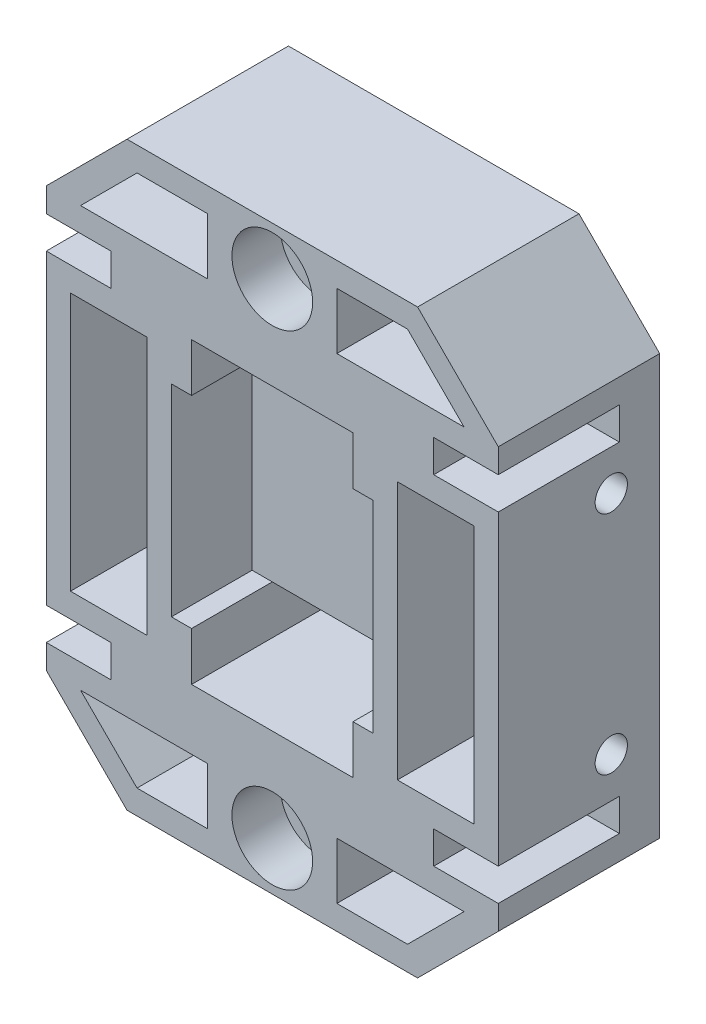
SolidWorks part; units mm, degrees
ref_plane "Plano frontal" through (0, 0, 0) normal (0, 0, 1) x (1, 0, 0)
ref_plane "Plano superior" through (0, 0, 0) normal (0, 1, 0) x (1, 0, 0)
ref_plane "Plano direito" through (0, 0, 0) normal (1, 0, 0) x (0, 0, -1)
sketch "Esboço1" plane through (0, 0, 0) normal (0, 0, 1) x (1, 0, 0)
  line L1 (-14, -18) -> (14, -18)
  line L2 (-14, -18) -> (-14, 18)
  line L3 (-14, 18) -> (14, 18)
  line L4 (14, -18) -> (14, 18)
  line L5 (-14, -18) -> (14, 18) construction
  line L6 (-14, 18) -> (14, -18) construction
  point P0 (0, 0)
  dimension "D1" = 28
  dimension "D2" = 36
extrude "Ressalto-extrusão1" add sketch "Esboço1" along normal blind 10
sketch "Esboço2" plane through (0, 0, 10) normal (0, 0, 1) x (1, 0, 0)
  line L1 (-6.25, -6.25) -> (6.25, -6.25)
  line L2 (-6.25, -6.25) -> (-6.25, 6.25)
  line L3 (-6.25, 6.25) -> (6.25, 6.25)
  line L4 (6.25, -6.25) -> (6.25, 6.25)
  line L5 (-6.25, -6.25) -> (6.25, 6.25) construction
  line L6 (-6.25, 6.25) -> (6.25, -6.25) construction
  point P0 (0, 0)
  dimension "D1" = 12.5
  dimension "D2" = 12.5
extrude "Corte-extrusão1" cut sketch "Esboço2" against normal blind 5
sketch "Esboço3" plane through (0, 0, 10) normal (0, 0, 1) x (1, 0, 0)
  line L0 (6.25, 6.25) -> (-6.25, 6.25) construction
  line L1 (-5, 6.25) -> (5, 6.25)
  line L2 (-5, 6.25) -> (-5, 9.25)
  line L3 (-5, 9.25) -> (5, 9.25)
  line L4 (5, 6.25) -> (5, 9.25)
  line L5 (-6.25, 0) -> (6.25, 0) construction
  line L6 (-6.25, 6.25) -> (-6.25, -6.25) construction
  line L7 (6.25, -6.25) -> (6.25, 6.25) construction
  line L8 (5, -6.25) -> (5, -9.25)
  line L9 (-5, -9.25) -> (5, -9.25)
  line L10 (-5, -6.25) -> (-5, -9.25)
  line L11 (-5, -6.25) -> (5, -6.25)
  dimension "D1" = 3
  dimension "D2" = 5
  dimension "D3" = 5
extrude "Corte-extrusão2" cut sketch "Esboço3" against normal through all
sketch "Esboço4" plane through (-14, 0, 0) normal (-1, 0, 0) x (0, 0, 1)
  line L0 (0, 0) -> (10, 0) construction
  line L1 (10, 18) -> (10, -18) construction
  circle A0 centre (3, 7) radius 1
  circle A1 centre (3, -7) radius 1
  point P7 (5, 0)
  dimension "D1" = 2
  dimension "D2" = 2
  dimension "D3" = 7
extrude "Corte-extrusão3" cut sketch "Esboço4" against normal blind 5
mirror "Espelhar1" about plane through (0, 0, 0) normal (1, 0, 0) of "Corte-extrusão3"
sketch "Esboço5" plane through (0, 0, 10) normal (0, 0, 1) x (1, 0, 0)
  line L0 (-14, 18) -> (-14, -18) construction
  line L1 (-14, 11.5) -> (-10, 11.5)
  line L2 (-14, 11.5) -> (-14, 9.5)
  line L3 (-14, 9.5) -> (-10, 9.5)
  line L4 (-10, 11.5) -> (-10, 9.5)
  line L5 (-14, 0) -> (14, 0) construction
  line L6 (14, -18) -> (14, 18) construction
  line L7 (0, 18) -> (0, -18) construction
  line L8 (14, 18) -> (-14, 18) construction
  line L9 (-14, -18) -> (14, -18) construction
  line L10 (10, 11.5) -> (10, 9.5)
  line L11 (14, 9.5) -> (10, 9.5)
  line L12 (14, 11.5) -> (14, 9.5)
  line L13 (14, 11.5) -> (10, 11.5)
  line L14 (14, -11.5) -> (10, -11.5)
  line L15 (14, -11.5) -> (14, -9.5)
  line L16 (14, -9.5) -> (10, -9.5)
  line L17 (10, -11.5) -> (10, -9.5)
  line L18 (-10, -11.5) -> (-10, -9.5)
  line L19 (-14, -9.5) -> (-10, -9.5)
  line L20 (-14, -11.5) -> (-14, -9.5)
  line L21 (-14, -11.5) -> (-10, -11.5)
  dimension "D1" = 4
  dimension "D2" = 2
  dimension "D3" = 9.5
extrude "Corte-extrusão4" cut sketch "Esboço5" against normal blind 7.5
sketch "Esboço6" plane through (0, 0, 10) normal (0, 0, 1) x (1, 0, 0)
  line L0 (-14, 0) -> (14, 0) construction
  line L1 (-14, 9.5) -> (-14, -9.5) construction
  line L2 (14, -9.5) -> (14, 9.5) construction
  circle A0 centre (0, 15) radius 2.5
  circle A1 centre (0, -15) radius 2.5
  dimension "D1" = 15
  dimension "D2" = 5
extrude "Corte-extrusão5" cut sketch "Esboço6" against normal blind 3
chamfer "Chanfro1" distance 5 angle 45 4 edges at (-14, -18, 5) (14, -18, 5) (14, 18, 5) (-14, 18, 5)
sketch "Esboço7" plane through (0, 0, 10) normal (0, 0, 1) x (1, 0, 0)
  line L0 (0, 18) -> (0, -18) construction
  line L1 (-12.5, 8) -> (-7.75, 8)
  line L2 (-12.5, 8) -> (-12.5, -8)
  line L3 (-12.5, -8) -> (-7.75, -8)
  line L4 (-7.75, 8) -> (-7.75, -8)
  line L5 (9, 18) -> (-9, 18) construction
  line L6 (-9, -18) -> (9, -18) construction
  line L7 (7.75, 8) -> (7.75, -8)
  line L8 (12.5, -8) -> (7.75, -8)
  line L9 (12.5, 8) -> (12.5, -8)
  line L10 (12.5, 8) -> (7.75, 8)
  line L11 (-6.25, 6.25) -> (-6.25, -6.25) construction
  line L12 (-14, 9.5) -> (-14, -9.5) construction
  line L13 (-14, 9.5) -> (-10, 9.5) construction
  line L14 (-10, -9.5) -> (-14, -9.5) construction
  dimension "D1" = 1.5
  dimension "D2" = 1.5
  dimension "D3" = 1.5
  dimension "D4" = 1.5
extrude "Corte-extrusão6" cut sketch "Esboço7" against normal blind 5
sketch "Esboço8" plane through (0, 0, 10) normal (0, 0, 1) x (1, 0, 0)
  line L24 (-11.8787, 13) -> (-8.3787, 16.5)
  line L25 (-8.3787, 16.5) -> (-4, 16.5)
  line L26 (-4, 16.5) -> (-4, 13)
  line L27 (-4, 13) -> (-11.8787, 13)
  line L28 (0, 18) -> (0, -18) construction
  line L29 (9, 18) -> (-9, 18) construction
  line L30 (-9, -18) -> (9, -18) construction
  line L31 (-14, 0) -> (14, 0) construction
  line L32 (-14, 9.5) -> (-14, -9.5) construction
  line L33 (14, -9.5) -> (14, 9.5) construction
  line L34 (-9, 18) -> (-14, 13) construction
  line L35 (-10, 11.5) -> (-14, 11.5) construction
  line L36 (4, 13) -> (11.8787, 13)
  line L37 (4, 16.5) -> (4, 13)
  line L38 (8.3787, 16.5) -> (4, 16.5)
  line L39 (11.8787, 13) -> (8.3787, 16.5)
  line L40 (11.8787, -13) -> (8.3787, -16.5)
  line L41 (8.3787, -16.5) -> (4, -16.5)
  line L42 (4, -16.5) -> (4, -13)
  line L43 (4, -13) -> (11.8787, -13)
  line L44 (-4, -13) -> (-11.8787, -13)
  line L45 (-4, -16.5) -> (-4, -13)
  line L46 (-8.3787, -16.5) -> (-4, -16.5)
  line L47 (-11.8787, -13) -> (-8.3787, -16.5)
  dimension "D1" = 1.5
  dimension "D2" = 1.5
  dimension "D3" = 1.5
  dimension "D4" = 4
extrude "Corte-extrusão7" cut sketch "Esboço8" against normal blind 8
